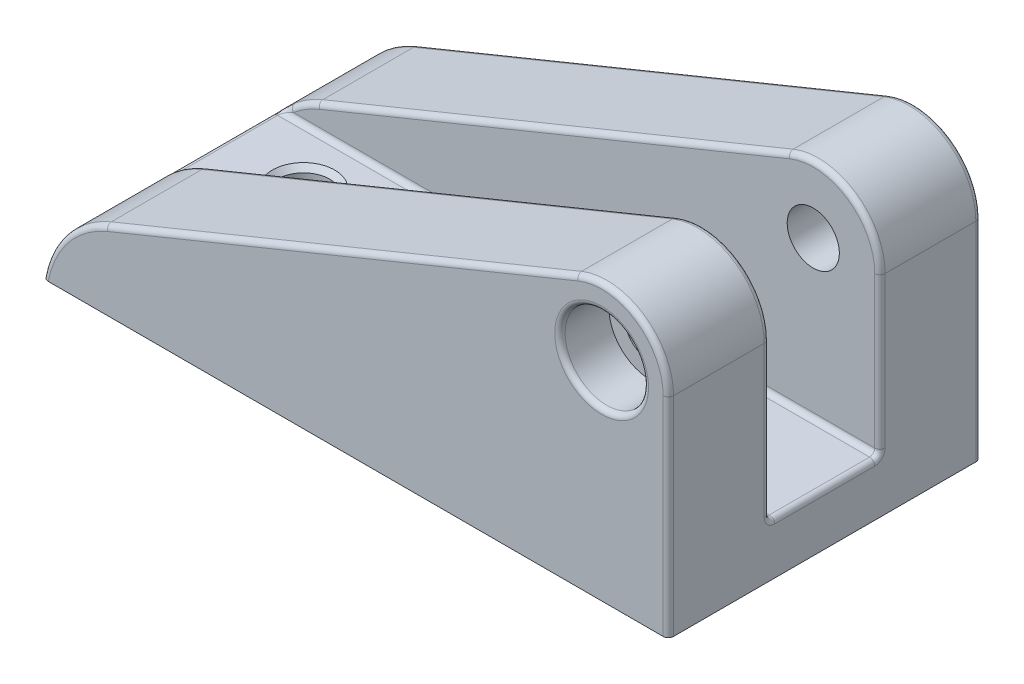
SolidWorks part; units mm, degrees
material "Nylon 101"
ref_plane "Front Plane" through (0, 0, 0) normal (0, 0, 1) x (1, 0, 0)
ref_plane "Top Plane" through (0, 0, 0) normal (0, 1, 0) x (1, 0, 0)
ref_plane "Right Plane" through (0, 0, 0) normal (1, 0, 0) x (0, 0, -1)
sketch "Sketch4" plane through (0, 0, 0) normal (0, 0, 1) x (1, 0, 0)
  line L0 (64.996, 32.9235) -> (0, 6.35)
  line L1 (0, 0) -> (76.2, 0)
  line L2 (0, 0) -> (0, 33.528)
  line L3 (0, 33.528) -> (76.2, 33.528)
  line L4 (76.2, 0) -> (76.2, 33.528)
  circle A0 centre (68.072, 25.4) radius 3.175
  circle A1 centre (68.072, 25.4) radius 8.128
  circle A2 centre (68.072, 25.4) radius 5.08
  dimension "D3" = 6.35
  dimension "D4" = 8.128
  dimension "D6" = 10.16
  dimension "D1" = 25.4
  dimension "D2" = 76.2
  dimension "D5" = 6.35
extrude "Boss-Extrude1" add sketch "Sketch4" along normal mid plane 38.1 contours A1 L0 L2 L1 L4 | A1 A0 | A2 A0
sketch "Sketch5" plane through (0, 0, 0) normal (1, 0, 0) x (0, 0, -1)
  line L0 (19.05, 33.528) -> (-19.05, 33.528) construction
  line L1 (-6.731, 33.528) -> (6.731, 33.528)
  line L2 (-6.731, 33.528) -> (-6.731, 6.35)
  line L3 (-6.731, 6.35) -> (6.731, 6.35)
  line L4 (6.731, 33.528) -> (6.731, 6.35)
  line L5 (-19.05, 0) -> (19.05, 0) construction
  point P4 (0, 6.35)
  dimension "D1" = 13.462
  dimension "D2" = 6.35
extrude "Cut-Extrude2" cut sketch "Sketch5" against normal through all and the other way through all
sketch "Sketch10" plane through (0, 0, 19.05) normal (0, 0, 1) x (1, 0, 0)
  circle A0 centre (68.072, 25.4) radius 5.08 construction
  circle A1 centre (68.072, 25.4) radius 5.08
extrude "Cut-Extrude5" cut sketch "Sketch10" against normal offset from surface (5.969 mm away) 6.35 up to face at (68.072, 22.225, 6.731)
sketch "Sketch9" plane through (0, 0, -19.05) normal (0, 0, -1) x (-1, 0, 0)
  line L1 (-64.8641, 30.9562) -> (-71.2799, 30.9562)
  line L2 (-71.2799, 30.9562) -> (-74.4878, 25.4)
  line L3 (-74.4878, 25.4) -> (-71.2799, 19.8437)
  line L4 (-71.2799, 19.8437) -> (-64.8641, 19.8437)
  line L5 (-64.8641, 19.8437) -> (-61.6562, 25.4)
  line L6 (-61.6562, 25.4) -> (-64.8641, 30.9562)
  circle A0 centre (-68.072, 25.4) radius 5.5563 construction
  dimension "D1" = 11.1125
extrude "Cut-Extrude4" cut sketch "Sketch9" against normal offset from surface (5.969 mm away) 6.35 up to face at (68.072, 28.575, -6.731)
sketch "Sketch6" plane through (0, 0, 0) normal (0, 1, 0) x (1, 0, 0)
  line L0 (0, 0) -> (76.2, 0) construction
  line L1 (76.2, -6.731) -> (76.2, 6.731) construction
  point P5 (12.7, 0)
  point P6 (50.8, 0)
  dimension "D1" = 12.7
  dimension "D2" = 50.8
hole_wizard "1/4 (0.25) Diameter Hole1" positions "Sketch7" profile "Sketch8" hole size "1/4" standard "ANSI Inch"
sketch "Sketch7" plane through (0, 6.35, 0) normal (0, 1, 0) x (1, 0, 0)
  point P0 (12.7, 0)
  point P3 (50.8, 0)
sketch "Sketch8" plane through (12.7, 6.35, 0) normal (1, 0, 0) x (0, 0, 1)
  line L0 (0, 0) -> (0, 26.2917)
  line L1 (0, 26.2917) -> (3.175, 24.384)
  line L2 (3.175, 24.384) -> (3.175, 0.635)
  line L3 (3.175, 0.635) -> (3.81, 0)
  line L5 (3.81, 0) -> (0, 0)
  line L6 (-3.175, 0.635) -> (-3.81, 0) construction
  line L10 (0, 26.2917) -> (-3.175, 24.384) construction
  line L11 (0, -6.35) -> (0, 107.95) construction
  dimension "Hole Dia." = 6.35
  dimension "Hole Depth" = 24.384
  dimension "Near C'Sink Dia." = 7.62
  dimension "Near C'Sink Angle" = 90
  dimension "Drill Angle" = 118
fillet "Fillet1" radius 12.7 2 edges at (0, 6.35, 12.8905) (0, 6.35, -12.8905)
fillet "Fillet3" radius 0.635 27 edges at (76.2, 12.7, 19.05) (76.2, 12.7, -19.05) (72.6032, 32.1478, -6.731) (72.6032, 32.1478, -19.05) (72.6032, 32.1478, 6.731) (72.6032, 32.1478, 19.05) (2.6286, 5.7329, 19.05) (2.6286, 5.7329, -19.05) (76.2, 15.875, 6.731) (5.2539, 8.1709, 6.731) (5.2539, 8.1709, -6.731) (76.2, 15.875, -6.731) (76.2, 6.35, 0) (39.6811, 6.35, 6.731) (3.1622, 6.35, 0) (39.6811, 6.35, -6.731) (36.3435, 21.209, -19.05) (36.3435, 21.209, -6.731) (36.3435, 21.209, 6.731) (36.3435, 21.209, 19.05) (72.8839, 28.1781, -19.05) (72.8839, 22.6219, -19.05) (68.072, 19.8437, -19.05) (63.2601, 28.1781, -19.05) (68.072, 30.9562, -19.05) (63.2601, 22.6219, -19.05) (73.152, 25.4, 19.05)
